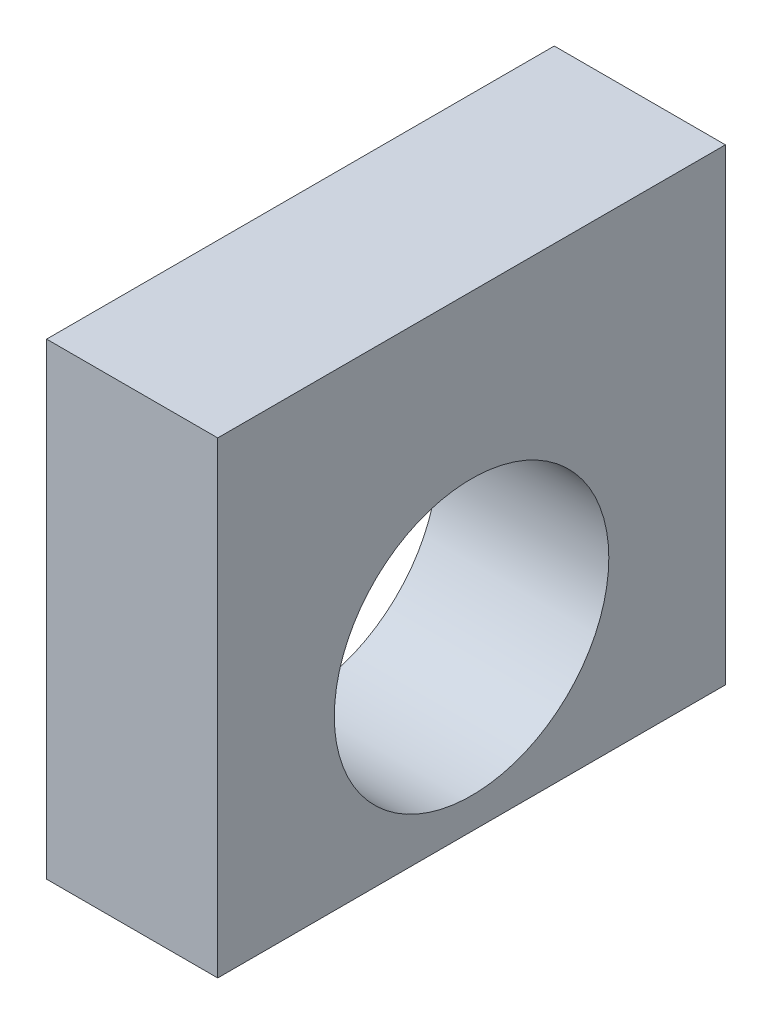
SolidWorks part; units mm, degrees
ref_plane "Front Plane" through (0, 0, 0) normal (0, 0, 1) x (1, 0, 0)
ref_plane "Top Plane" through (0, 0, 0) normal (0, 1, 0) x (1, 0, 0)
ref_plane "Right Plane" through (0, 0, 0) normal (1, 0, 0) x (0, 0, -1)
sketch "Block Sketch" plane through (0, 0, 0) normal (1, 0, 0) x (0, 0, -1)
  line L0 (8.9, 82.1) -> (-8.9, 82.1)
  line L1 (-8.9, 82.1) -> (-8.9, 98.5)
  line L2 (-8.9, 98.5) -> (8.9, 98.5)
  line L3 (8.9, 98.5) -> (8.9, 82.1)
extrude "Block" add sketch "Block Sketch" along normal mid plane 6
ref_axis "Engine Axis" through (3.3, 0, 0) along (-1, 0, 0)
sketch "Tube Hole Sketch" plane through (0, 0, 0) normal (1, 0, 0) x (0, 0, -1)
  circle A0 centre (0, 88) radius 4.8125
extrude "Tube Hole" cut sketch "Tube Hole Sketch" against normal mid plane 8
